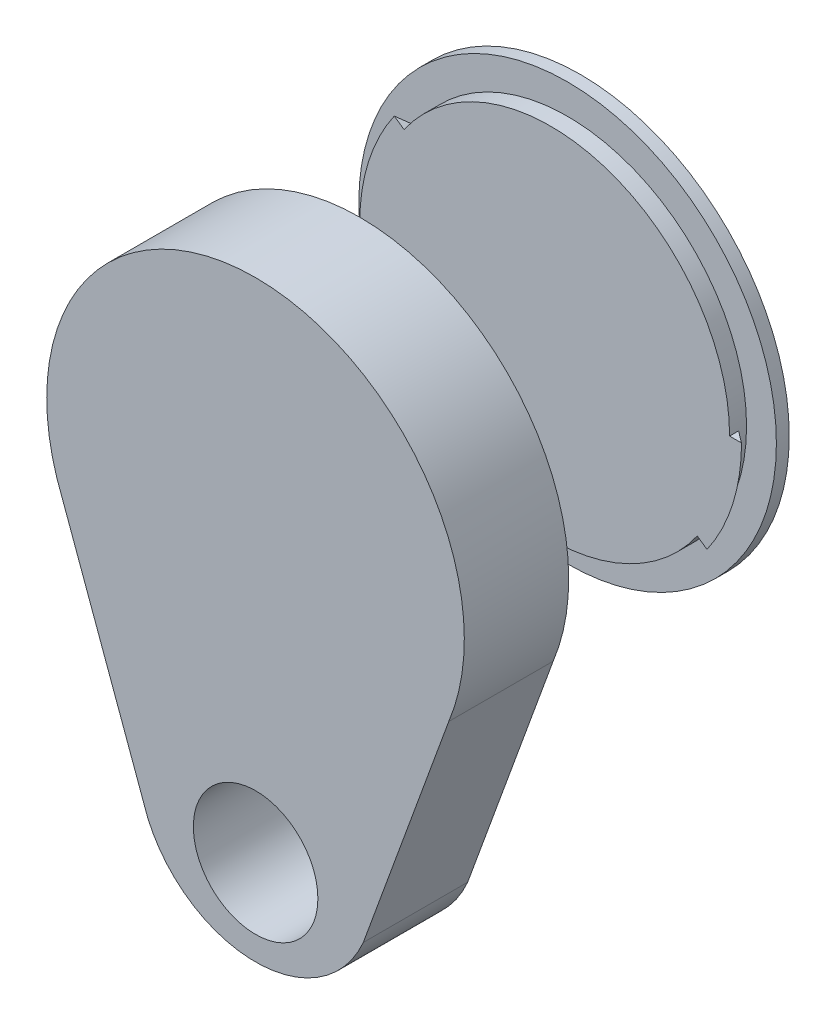
SolidWorks part; units mm, degrees
ref_plane "Plan de face" through (0, 0, 0) normal (0, 0, 1) x (1, 0, 0)
ref_plane "Plan de dessus" through (0, 0, 0) normal (0, 1, 0) x (1, 0, 0)
ref_plane "Plan de droite" through (0, 0, 0) normal (1, 0, 0) x (0, 0, -1)
sketch "Esquisse1" plane through (1.309, 0, 0) normal (0, 1, 0) x (1, 0, 0)
  line L0 (0.2535, -3.046) -> (-13.7465, -3.046)
  line L1 (-13.7465, -3.046) -> (-13.7465, 3.954)
  line L2 (-13.7465, 3.954) -> (-12.7465, 3.954)
  line L4 (-12.7465, 3.954) -> (-12.7465, 3.4429)
  line L5 (-12.7465, 3.4429) -> (-12.7465, 2.954)
  line L6 (-12.7465, 2.954) -> (-12.7465, -2.046)
  line L7 (-12.7465, -2.046) -> (0.2535, -2.046)
  line L8 (0.2535, -2.046) -> (0.2535, -3.046)
  dimension "D1" = 14
  dimension "D2" = 1
  dimension "D3" = 1
  dimension "D4" = 7
  dimension "D5" = 5
  dimension "D8" = 1
revolve "Révolution1" add sketch "Esquisse1" angle 360 about L8
sketch "Esquisse2" plane through (0, 0, -11.8007) normal (0, 1, 0) x (1, 0, 0)
  line L0 (0.6636, 5.8413) -> (-11.3364, 5.8413)
  line L1 (-11.3364, 5.8413) -> (-11.3364, 6.3655)
  line L2 (-11.3364, 6.3655) -> (-11.3364, 6.9783)
  line L3 (-11.3364, 6.9783) -> (-13.3364, 6.9783)
  line L4 (-13.3364, 6.9783) -> (-13.3364, 7.8413)
  line L5 (-13.3364, 7.8413) -> (0.6636, 7.8413)
  line L6 (0.6636, 7.8413) -> (0.6636, 5.8413)
  dimension "D1" = 2
  dimension "D2" = 12
  dimension "D3" = 2
  dimension "D5" = 14
revolve "Révolution2" add sketch "Esquisse2" angle 360 about L6
ref_plane "Plan1" through (0, 0, 3.046) normal (0, 0, 1) x (1, 0, 0)
ref_plane "Plan2" through (0, 0, 2.046) normal (0, 0, 1) x (1, 0, 0)
sketch "Esquisse10" plane through (0, 0, 3.046) normal (0, 0, 1) x (1, 0, 0)
  line L0 (14.8888, -4.2906) -> (8.7888, -21)
  line L1 (-5.6638, -21) -> (-11.7638, -4.2906)
  line L2 (1.5625, 0) -> (-12.4375, 0) construction
  arc A0 (14.8888, -4.2906) -> (-11.7638, -4.2906) centre (1.5625, 1.1242) cw
  circle A1 centre (1.5625, 0) radius 14 construction
  arc A2 (8.7888, -21) -> (-5.6638, -21) centre (1.5625, -17.8753) cw
  dimension "D1" = 21
  dimension "D2" = 21
extrude "Boss.-Extru.4" add sketch "Esquisse10" against normal blind 7
sketch "Esquisse11" plane through (0, 0, 3.046) normal (0, 0, 1) x (1, 0, 0)
  circle A0 centre (1.5688, -19.9708) radius 4.1753
  arc A1 (-5.6638, -21) -> (8.7888, -21) centre (1.5625, -17.8753) ccw construction
  point P2 (1.5625, -25.7482)
  dimension "D1" = 5.7775
  dimension "D2" = 7.22
  dimension "D3" = 7.2326
extrude "Enlèv. mat.-Extru.2" cut sketch "Esquisse11" against normal blind 7
ref_axis "Axe1" through (0.6636, 0, -17.642) along (0, 0, -1)
sketch "Esquisse13" plane through (0, 0, 0) normal (0, 1, 0) x (1, 0, 0)
  line L0 (-11.3364, 17.642) -> (-12.1364, 17.642)
  line L1 (-12.1364, 17.642) -> (-11.3364, 18.242)
  line L2 (-11.3364, 18.779) -> (-11.3364, 17.642) construction
  line L3 (-11.3364, 18.242) -> (-11.3364, 17.642)
  dimension "D1" = 0.6
  dimension "D2" = 0.8
revolve "Révolution3" add sketch "Esquisse13" angle 35 about axis through (0.6636, 0, -17.642) along (0, 0, -1)
pattern_circular "Répétition circulaire1" count 2 over 360 about axis through (0.6636, 0, -17.642) along (0, 0, -1) of "Révolution3"
sketch "Esquisse14" plane through (0, 0, 0) normal (0, 1, 0) x (1, 0, 0)
  line L0 (-11.4375, 3.954) -> (-10.4375, 3.954)
  line L1 (15.5625, 3.954) -> (-12.4375, 3.954) construction
  line L2 (-10.4375, 3.954) -> (-11.4375, 3.454)
  line L4 (-11.4375, 3.454) -> (-11.4375, 3.954)
  dimension "D1" = 1
  dimension "D2" = 0.5
ref_axis "Axe2" through (1.5625, 0, 2.046) along (0, 0, -1)
revolve "Révolution4" add sketch "Esquisse14" angle 140 about axis through (1.5625, 0, 2.046) along (0, 0, -1) other way angle 140
pattern_circular "Répétition circulaire2" count 2 every 180 about axis through (1.5625, 0, 2.046) along (0, 0, -1) of "Révolution4"
equation "\"4.5.00mm\"=4"
